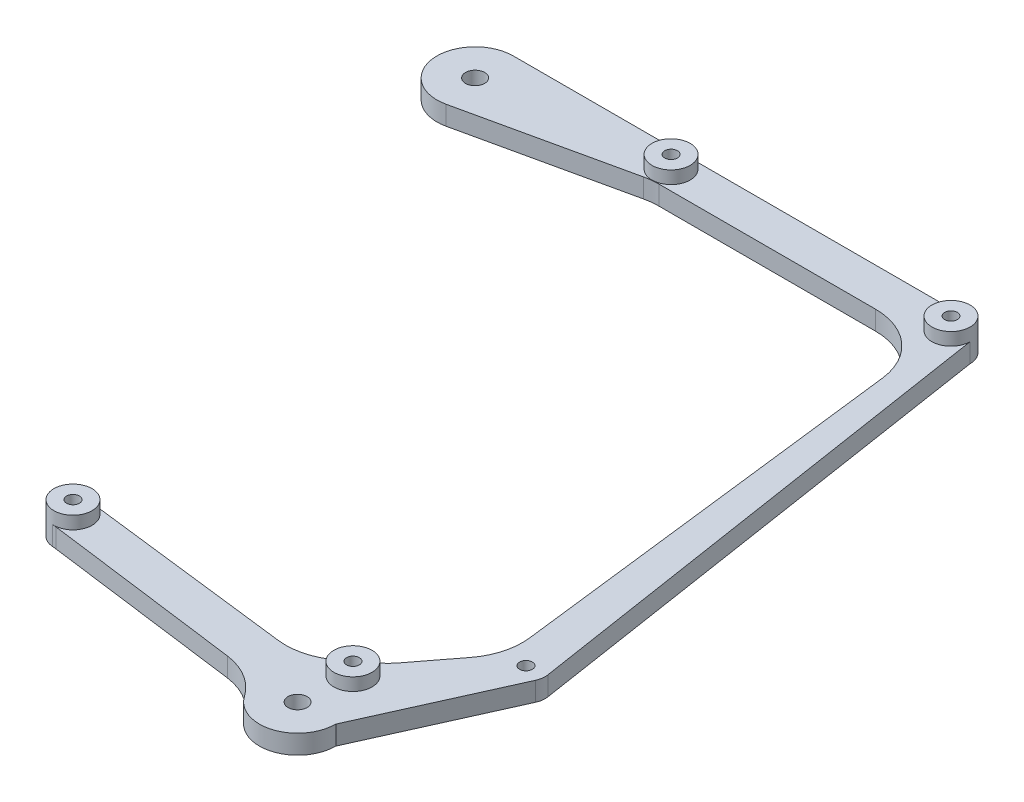
SolidWorks part; units mm, degrees
ref_plane "Front Plane" through (0, 0, 0) normal (0, 0, 1) x (1, 0, 0)
ref_plane "Top Plane" through (0, 0, 0) normal (0, 1, 0) x (1, 0, 0)
ref_plane "Right Plane" through (0, 0, 0) normal (1, 0, 0) x (0, 0, -1)
sketch "Sketch1" plane through (0, 53.5, 0) normal (0, 1, 0) x (1, 0, 0)
  circle A0 centre (-36, -88.75) radius 1.5 construction
  circle A1 centre (-36, -88.75) radius 6 construction
  circle A2 centre (35, 10.15) radius 1.5 construction
  circle A3 centre (35, 10.15) radius 6 construction
  circle A4 centre (106, -88.75) radius 1.5 construction
  circle A5 centre (106, -88.75) radius 6 construction
  circle A6 centre (-36, -88.75) radius 1.5
  circle A7 centre (-36, -88.75) radius 6
  circle A8 centre (35, 10.15) radius 1.5
  circle A9 centre (35, 10.15) radius 6
  circle A10 centre (106, -88.75) radius 1.5
  circle A11 centre (106, -88.75) radius 6
  circle A12 centre (119, -65.85) radius 1 construction
  circle A13 centre (-49, -65.85) radius 1 construction
  circle A14 centre (119, -65.85) radius 1
  circle A15 centre (-49, -65.85) radius 1
  circle A16 centre (119, -65.85) radius 3
  circle A17 centre (-49, -65.85) radius 3
  dimension "D1" = 2
  dimension "D2" = 2
extrude "AudioHolder links" add sketch "Sketch1" along normal blind 3
sketch "Limit profile" plane through (0, 53.5, 0) normal (0, -1, 0) x (1, 0, 0)
  line L4 (-47, 8.35) -> (117, 8.35)
  line L5 (117, 8.35) -> (117, 123.35)
  line L6 (117, 123.35) -> (-47, 123.35)
  line L7 (-47, 123.35) -> (-47, 8.35)
  line L8 (-47, 8.35) -> (117, 8.35)
  line L9 (117, 8.35) -> (117, 123.35)
  line L10 (117, 123.35) -> (-47, 123.35)
  line L11 (-47, 123.35) -> (-47, 8.35)
  dimension "D1" = 0
sketch "Sketch3" plane through (0, 56.5, 0) normal (0, 1, 0) x (1, 0, 0)
  line L0 (117, -8.35) -> (117, -123.35) construction
  line L1 (38.8, 16.55) -> (117, 16.55) construction
  line L2 (38.8, 16.55) -> (38.8, -84.25) construction
  line L3 (38.8, -84.25) -> (117, -84.25) construction
  line L4 (117, 16.55) -> (117, -84.25) construction
  line L5 (62.8, 13.15) -> (106.8, 13.15) construction
  line L6 (62.8, 13.15) -> (62.8, -80.85) construction
  line L7 (62.8, -80.85) -> (106.8, -80.85) construction
  line L8 (106.8, 13.15) -> (106.8, -80.85) construction
  line L10 (35, 16.15) -> (62.8, 16.15) construction
  circle A0 centre (106.8, 13.15) radius 1
  circle A1 centre (62.8, 13.15) radius 1
  circle A2 centre (62.8, -80.85) radius 1
  circle A3 centre (106.8, -80.85) radius 1
  circle A4 centre (106.8, 13.15) radius 3
  circle A5 centre (62.8, 13.15) radius 3
  circle A6 centre (62.8, -80.85) radius 3
  circle A7 centre (106.8, -80.85) radius 3
  circle A8 centre (35, 10.15) radius 6 construction
  circle A9 centre (35, 10.15) radius 6 construction
  point P4 (62.8, -33.85)
  point P9 (38.8, -33.85)
  dimension "D7" = 2
  dimension "D8" = 2
  dimension "D1" = 78.2
  dimension "D2" = 100.8
  dimension "D3" = 44
  dimension "D4" = 94
  dimension "D5" = 10.2
extrude "Modem standoffs" add sketch "Sketch3" along normal blind 2 and the other way up to surface (3 mm away) other way up to face at (106, 53.5, 94.75)
sketch "Sketch4" plane through (0, 53.5, 0) normal (0, -1, 0) x (1, 0, 0)
  line L0 (109.8, -13.15) -> (121.9647, 65.3908)
  line L1 (112, 88.75) -> (121.7365, 67.0795)
  line L2 (106.8, 77.85) -> (116, 65.85)
  line L3 (116, 65.85) -> (106.8, -10.15)
  line L4 (106.8, -16.15) -> (62.8, -16.15)
  line L5 (62.8, -16.15) -> (35, -16.15)
  line L6 (100, 88.75) -> (62.8, 83.85)
  line L7 (63.162, 77.8719) -> (104.6199, 82.9109)
  line L8 (36.295, -4.2914) -> (62.8, -10.15)
  line L9 (62.8, -10.15) -> (106.8, -10.15)
  circle A0 centre (119, 65.85) radius 1 construction
  circle A1 centre (119, 65.85) radius 3 construction
  circle A2 centre (106.8, -13.15) radius 1 construction
  circle A3 centre (106.8, -13.15) radius 3 construction
  circle A4 centre (62.8, -13.15) radius 1 construction
  circle A5 centre (62.8, -13.15) radius 3 construction
  circle A6 centre (35, -10.15) radius 1.5 construction
  circle A7 centre (35, -10.15) radius 6 construction
  circle A8 centre (119, 65.85) radius 1
  arc A9 (121.9647, 65.3908) -> (121.7365, 67.0795) centre (119, 65.85) ccw
  circle A10 centre (106.8, -13.15) radius 1
  arc A11 (106.8, -16.15) -> (109.8, -13.15) centre (106.8, -13.15) ccw
  circle A12 centre (62.8, -13.15) radius 1
  circle A14 centre (35, -10.15) radius 1.5
  arc A15 (36.295, -4.2914) -> (35, -16.15) centre (35, -10.15) ccw
  circle A16 centre (106, 88.75) radius 1.5 construction
  arc A17 (108.5227, 83.3061) -> (104.6199, 82.9109) centre (106, 88.75) ccw construction
  circle A18 centre (106.8, 80.85) radius 3 construction
  circle A19 centre (106.8, 80.85) radius 1 construction
  circle A20 centre (62.8, 80.85) radius 1 construction
  circle A21 centre (62.8, 80.85) radius 3 construction
  circle A22 centre (106, 88.75) radius 1.5
  arc A23 (112, 88.75) -> (100, 88.75) centre (106, 88.75) ccw
  arc A24 (104.6199, 82.9109) -> (106.8, 77.85) centre (106.8, 80.85) ccw
  circle A25 centre (106.8, 80.85) radius 1
  circle A26 centre (62.8, 80.85) radius 1
  arc A27 (62.8, 83.85) -> (63.162, 77.8719) centre (62.8, 80.85) ccw
extrude "Screwhole links 1" add sketch "Sketch4" against normal up to surface (3 mm away) up to face at (105.9466, 56.5, 89.2771)
sketch "Sketch5" plane through (0, 53.5, 0) normal (0, -1, 0) x (1, 0, 0)
  line L0 (59.8055, 80.6687) -> (29.3245, -8.2035)
  line L1 (63.162, 77.8719) -> (35, -16.15)
  arc A0 (62.8, 83.85) -> (63.162, 77.8719) centre (62.8, 80.85) ccw construction
  circle A1 centre (35, -10.15) radius 6 construction
  arc A2 (35, -16.15) -> (29.3245, -8.2035) centre (35, -10.15) ccw
  arc A3 (59.8055, 80.6687) -> (63.162, 77.8719) centre (62.8, 80.85) ccw
extrude "Screwhole links 2" add sketch "Sketch5" against normal up to surface (3 mm away) rebuild error yes up to face at (46.8207, 56.5, -11.5048)
sketch "Sketch6" plane through (0, 53.5, 0) normal (0, -1, 0) x (1, 0, 0)
  circle A0 centre (-49, 65.85) radius 3 construction
  circle A1 centre (-36, 88.75) radius 6
  circle A2 centre (-36, 88.75) radius 6
  circle A3 centre (-49, 65.85) radius 3
  dimension "D1" = 0
extrude "Removal of unused links to layer below" cut sketch "Sketch6" against normal through all both and the other way through all
fillet "General rounding 10mm (will replace later)" radius 10 9 edges at (36.295, 55, -4.2914) (62.8, 55, -10.15) (106.8, 55, -10.15) (104.6199, 55, 82.9109) (106.8, 55, 77.85) (100, 55, 88.75) (62.8, 55, 83.85) (116, 55, 65.85) (63.162, 55, 77.8719)
